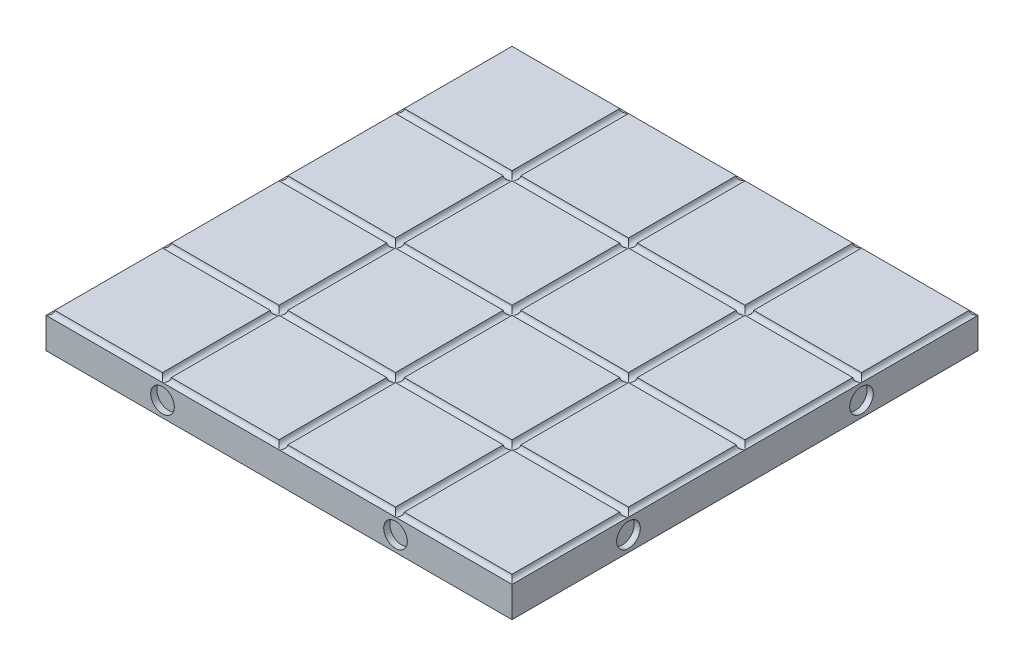
SolidWorks part; units mm, degrees
ref_plane "Спереди" through (0, 0, 0) normal (0, 0, 1) x (1, 0, 0)
ref_plane "Сверху" through (0, 0, 0) normal (0, 1, 0) x (1, 0, 0)
ref_plane "Справа" through (0, 0, 0) normal (1, 0, 0) x (0, 0, -1)
sketch "Эскиз1" plane through (0, 0, 0) normal (0, 1, 0) x (1, 0, 0)
  line L1 (80, -80) -> (-80, -80)
  line L2 (80, -80) -> (80, 80)
  line L3 (80, 80) -> (-80, 80)
  line L4 (-80, -80) -> (-80, 80)
  line L5 (0, 80) -> (0, -80) construction
  line L6 (80, 0) -> (-80, 0) construction
  point P0 (0, 0)
  dimension "D1" = 160
extrude "Бобышка-Вытянуть1" add sketch "Эскиз1" against normal blind 12
sketch "Эскиз2" plane through (0, 0, 0) normal (0, 1, 0) x (1, 0, 0)
  line L0 (-80, 80) -> (-80, -80)
sweep "Вырез-По траектории1" cut path "Эскиз2" circular profile diameter 3 parameters "D3"=3
pattern_linear "Линейный массив1" count 5 spacing 40 along (1, 0, 0) of "Вырез-По траектории1"
sketch "Эскиз180" plane through (0, 0, 0) normal (0, 1, 0) x (1, 0, 0)
  line L0 (-80, -80) -> (80, -80)
sweep "Вырез-По траектории2" cut path "Эскиз180" circular profile diameter 3 parameters "D3"=3
pattern_linear "Линейный массив2" count 5 spacing 40 along (1, 0, 0) count 5 spacing 40 along (0, 0, -1) of "Вырез-По траектории2"
sketch "Эскиз181" plane through (0, 0, 80) normal (0, 0, 1) x (1, 0, 0)
  line L0 (0, 22.1626) -> (0, -39.4564) construction
  line L3 (-40, -1.5) -> (-40, -6.75) construction
  line L4 (-40, -6.75) -> (-40, -12) construction
  line L5 (-80, -12) -> (80, -12) construction
  circle A0 centre (-40, -6.75) radius 4.05
  circle A1 centre (40, -6.75) radius 4.05
  dimension "D1" = 8.1
  dimension "D2" = 1.2
extrude "Вырез-Вытянуть1" cut sketch "Эскиз181" against normal blind 2.1
pattern_circular "Круговой массив1" count 4 over 360 about axis through (0, -12, 0) along (0, -1, 0) of "Вырез-Вытянуть1" other way count 4
